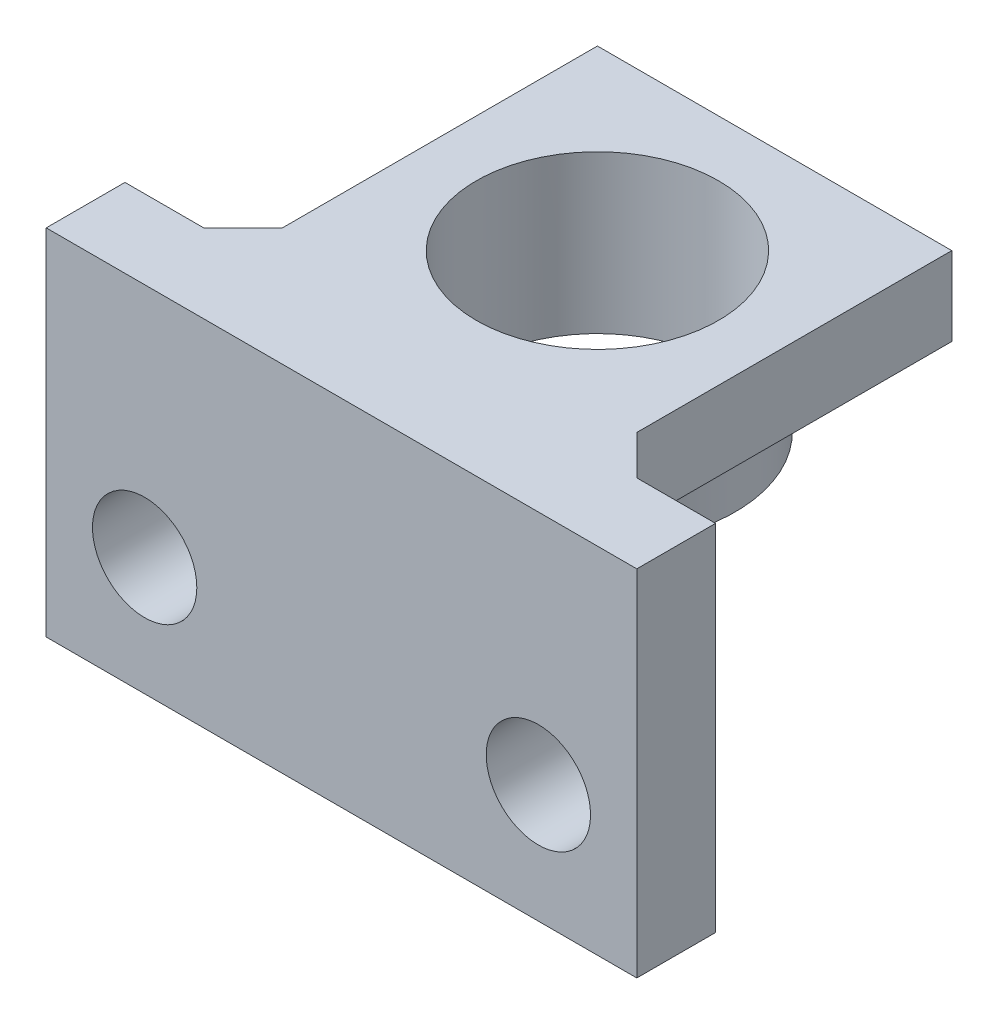
SolidWorks part; units mm, degrees
ref_plane "Front Plane" through (0, 0, 0) normal (0, 0, 1) x (1, 0, 0)
ref_plane "Top Plane" through (0, 0, 0) normal (0, 1, 0) x (1, 0, 0)
ref_plane "Right Plane" through (0, 0, 0) normal (1, 0, 0) x (0, 0, -1)
sketch "Sketch1" plane through (0, 0, 0) normal (0, 1, 0) x (1, 0, 0)
  line L0 (9, 18) -> (9, 0) construction
  line L1 (0, 0) -> (18, 0)
  line L2 (0, 0) -> (0, 18)
  line L3 (0, 18) -> (18, 18)
  line L4 (18, 0) -> (18, 18)
  line L5 (0, 9) -> (18, 9) construction
  circle A0 centre (9, 9) radius 6.15
  dimension "D1" = 12.3
  dimension "D2" = 18
  dimension "D3" = 18
extrude "Boss-Extrude1" add sketch "Sketch1" along normal blind 4
sketch "Sketch2" plane through (0, 0, 0) normal (0, 0, 1) x (1, 0, 0)
  line L1 (-6, 4) -> (24, 4)
  line L2 (-6, 4) -> (-6, -14)
  line L3 (-6, -14) -> (24, -14)
  line L4 (24, 4) -> (24, -14)
  line L5 (-6, -8) -> (24, -8) construction
  line L6 (9, 4) -> (9, -14) construction
  line L7 (9, 0) -> (9, 4) construction
  line L8 (0, 0) -> (18, 0) construction
  line L9 (0, 4) -> (18, 4) construction
  circle A0 centre (-1, -8) radius 2.65
  circle A1 centre (19, -8) radius 2.65
  dimension "D2" = 5.3
  dimension "D1" = 18
  dimension "D3" = 20
  dimension "D4" = 5
  dimension "D5" = 6
extrude "Boss-Extrude2" add sketch "Sketch2" along normal blind 4
sketch "Sketch3" plane through (0, 0, 0) normal (0, -1, 0) x (1, 0, 0)
  circle A1 centre (9, -9) radius 7
  circle A2 centre (9, -9) radius 6.15 construction
  circle A3 centre (9, -9) radius 6.15
  dimension "D1" = 14
extrude "Boss-Extrude3" add sketch "Sketch3" along normal blind 4
chamfer "Chamfer1" distance 2 angle 45 3 edges at (0, 2, 0) (9, 0, 0) (18, 2, 0)
